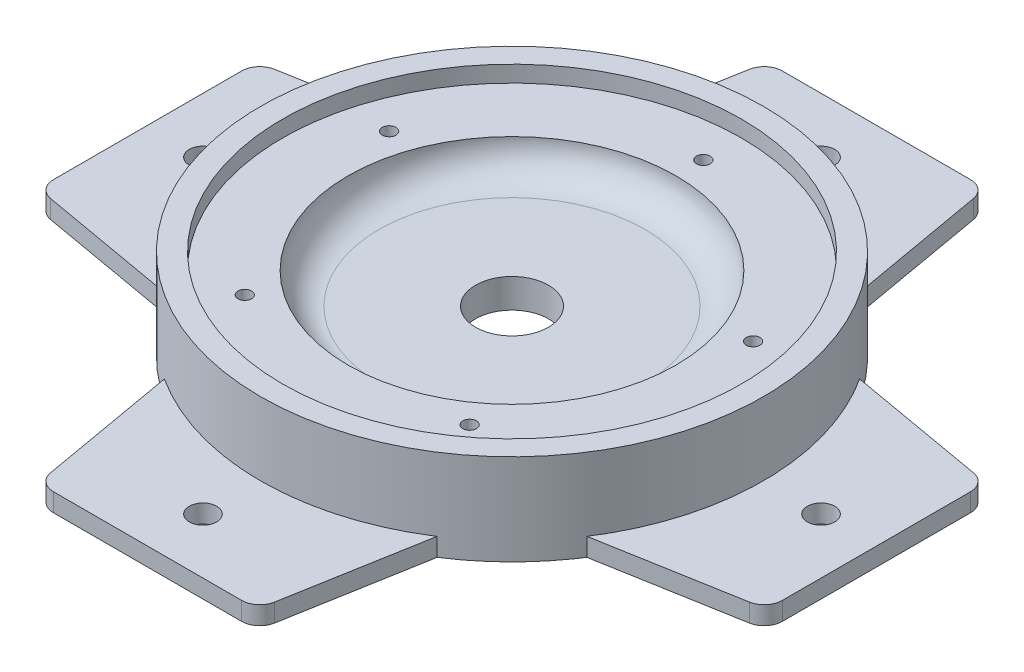
SolidWorks part; units mm, degrees
material "AISI 1020"
ref_plane "Front Plane" through (0, 0, 0) normal (0, 0, 1) x (1, 0, 0)
ref_plane "Top Plane" through (0, 0, 0) normal (0, 1, 0) x (1, 0, 0)
ref_plane "Right Plane" through (0, 0, 0) normal (1, 0, 0) x (0, 0, -1)
sketch "Sketch1" plane through (0, 0, 0) normal (0, 0, 1) x (1, 0, 0)
  line L0 (0, 92.5968) -> (0, -53.0582) construction
  line L2 (87.63, -5.08) -> (87.63, 26.67)
  line L4 (87.63, 26.67) -> (79.9719, 26.67)
  line L5 (79.9719, 26.67) -> (79.9719, 20.955)
  line L6 (79.9719, 20.955) -> (57.15, 20.955)
  line L7 (57.15, 20.955) -> (57.15, 10.16)
  line L8 (57.15, 10.16) -> (0, 10.16)
  line L9 (0, 10.16) -> (0, 0)
  line L10 (0, 0) -> (57.15, 0)
  line L11 (57.15, 0) -> (57.15, -5.08)
  line L12 (57.15, -5.08) -> (87.63, -5.08)
  dimension "D1" = 57.15
  dimension "D2" = 87.63
  dimension "D3" = 57.15
  dimension "D4" = 79.9719
  dimension "D5" = 10.16
  dimension "D6" = 20.955
  dimension "D7" = 31.75
  dimension "D8" = 5.715
revolve "Revolve1" add sketch "Sketch1" angle 360 about L0
hole_wizard "3/16 (0.1865) Diameter Hole1" positions "Sketch5" profile "Sketch6" hole size "3/16" standard "ANSI Inch"
sketch "Sketch5" plane through (0, 26.67, 0) normal (0, 1, 0) x (1, 0, 0)
  point P0 (0, 66.675)
  point P4 (-114.056, -74.738)
  dimension "D1" = 66.675
sketch "Sketch6" plane through (0, 26.67, -66.675) normal (1, 0, 0) x (0, 0, 1)
  line L0 (0, 0) -> (0, 11.0752)
  line L1 (0, 11.0752) -> (2.3685, 9.652)
  line L2 (2.3685, 9.652) -> (2.3685, 0)
  line L5 (2.3685, 0) -> (0, 0)
  line L10 (0, 11.0752) -> (-2.3686, 9.652) construction
  line L11 (0, -6.35) -> (0, 107.95) construction
  dimension "Hole Dia." = 4.7371
  dimension "Hole Depth" = 9.652
  dimension "Drill Angle" = 118
pattern_circular "CirPattern2" count 5 over 360 about axis through (0, 20.955, 0) along (0, 1, 0) of "3/16 (0.1865) Diameter Hole1"
hole_wizard "1 (1) Diameter Hole1" positions "Sketch7" profile "Sketch9" hole size "1" standard "ANSI Inch" end condition through all
sketch "Sketch7" plane through (0, 10.16, 0) normal (0, 1, 0) x (1, 0, 0)
  point P0 (0, 0)
sketch "Sketch9" plane through (0, 10.16, 0) normal (1, 0, 0) x (0, 0, 1)
  line L0 (0, 0) -> (0, 15.24)
  line L1 (0, 15.24) -> (12.7, 15.24)
  line L2 (12.7, 15.24) -> (12.7, 0)
  line L5 (12.7, 0) -> (0, 0)
  line L11 (0, -6.35) -> (0, 107.95) construction
  dimension "Thru Hole Dia." = 25.4
  dimension "Thru Hole Depth" = 15.24
sketch "Sketch14" plane through (0, 20.955, 0) normal (0, -1, 0) x (1, 0, 0)
  circle A0 centre (0, 0) radius 19.05
  dimension "D1" = 38.1
sketch "Sketch15" plane through (0, -5.08, 0) normal (0, -1, 0) x (1, 0, 0)
  line L4 (0, 0) -> (-157.4172, 0) construction
  line L6 (-127, -38.1) -> (-73.633, -47.51)
  line L9 (-127, 38.1) -> (-127, -38.1)
  line L10 (0, -17.4625) -> (0, 17.4625) construction
  line L11 (-127, 38.1) -> (-73.633, 47.51)
  circle A0 centre (0, 0) radius 87.63 construction
  arc A1 (-73.633, 47.51) -> (-73.633, -47.51) centre (0, 0) ccw
  dimension "D1" = 76.2
  dimension "D4" = 127
  dimension "D5" = 100
extrude "Boss-Extrude1" add sketch "Sketch15" against normal blind 6.35 separate body
fillet "Fillet2" radius 6.35 2 edges at (-127, -1.905, -38.1) (-127, -1.905, 38.1)
hole_wizard "3/8 (0.375) Diameter Hole1" positions "Sketch16" profile "Sketch17" hole size "3/8" standard "ANSI Inch"
sketch "Sketch16" plane through (0, 1.27, 0) normal (0, 1, 0) x (1, 0, 0)
  point P0 (-107.696, 0)
  dimension "D1" = 107.696
sketch "Sketch17" plane through (-107.696, 1.27, 0) normal (1, 0, 0) x (0, 0, 1)
  line L0 (0, 0) -> (0, 28.2616)
  line L1 (0, 28.2616) -> (4.7625, 25.4)
  line L2 (4.7625, 25.4) -> (4.7625, 0)
  line L5 (4.7625, 0) -> (0, 0)
  line L10 (0, 28.2616) -> (-4.7625, 25.4) construction
  line L11 (0, -6.35) -> (0, 107.95) construction
  dimension "Hole Dia." = 9.525
  dimension "Hole Depth" = 25.4
  dimension "Drill Angle" = 118
pattern_circular "CirPattern4" count 4 over 360 about axis through (0, 26.67, 0) along (0, 1, 0) of bodies 121
fillet "Fillet3" radius 10.795 2 edges at (0, 0, 57.15) (0, 10.16, 57.15)
